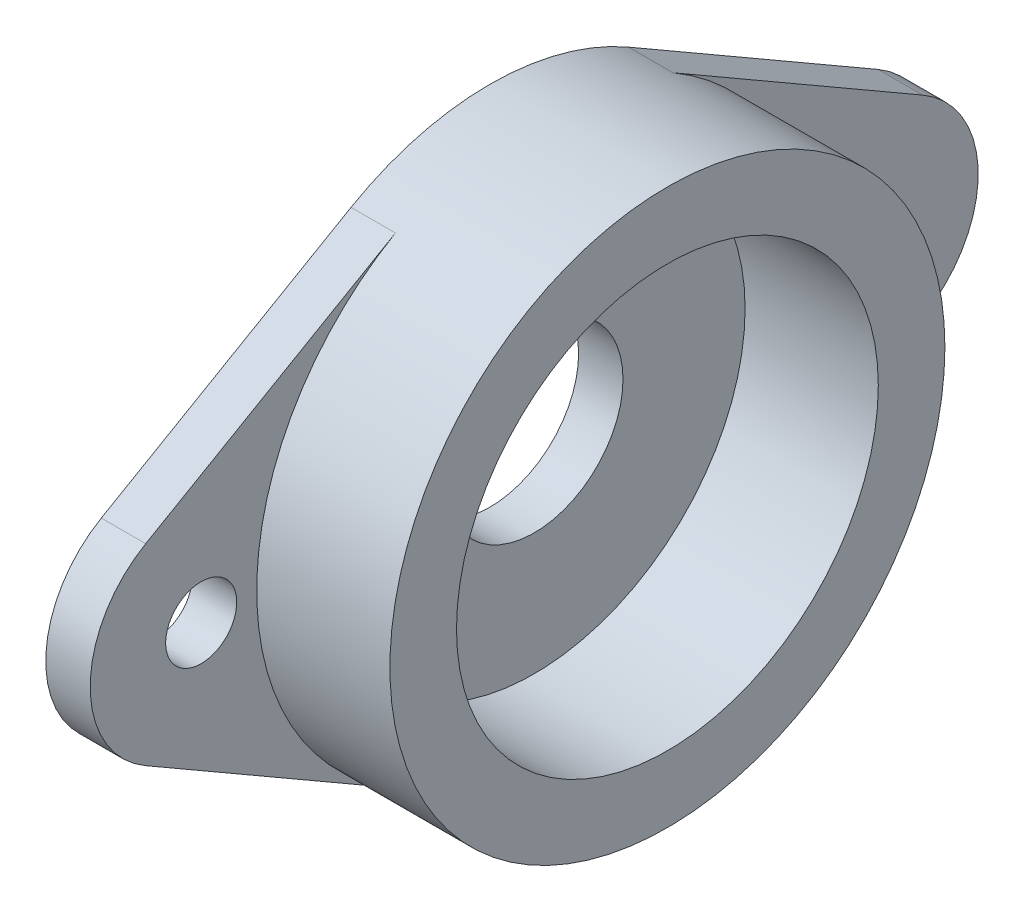
SolidWorks part; units mm, degrees
ref_plane "Front Plane" through (0, 0, 0) normal (0, 0, 1) x (1, 0, 0)
ref_plane "Top Plane" through (0, 0, 0) normal (0, 1, 0) x (1, 0, 0)
ref_plane "Right Plane" through (0, 0, 0) normal (1, 0, 0) x (0, 0, -1)
sketch "Sketch1" plane through (0, 0, 0) normal (1, 0, 0) x (0, 0, -1)
  line L0 (0, 0) -> (0, 7304.3141) construction
  line L1 (-17.5, 4.3301) -> (-6.25, 10.8253)
  line L2 (-17.5, -4.3301) -> (-6.25, -10.8253)
  line L3 (17.5, -4.3301) -> (6.25, -10.8253)
  line L4 (17.5, 4.3301) -> (6.25, 10.8253)
  circle A2 centre (0, 0) radius 9.5
  circle A3 centre (0, 0) radius 12.5
  arc A4 (-17.5, -4.3301) -> (-17.5, 4.3301) centre (-15, 0) cw
  circle A5 centre (-15, 0) radius 1.6
  circle A6 centre (15, 0) radius 1.6
  arc A7 (17.5, -4.3301) -> (17.5, 4.3301) centre (15, 0) ccw
  circle A8 centre (0, 0) radius 4
  dimension "D1" = 19
  dimension "D2" = 12.5
  dimension "D4" = 3.2
  dimension "D5" = 5
  dimension "D6" = 8
  dimension "D3" = 15
extrude "Boss-Extrude1" add sketch "Sketch1" along normal blind 2 contours A4 L2 A3 L1 A5 | L3 A7 L4 A3 A6 region at (0, 7.3556, 11.7468) region at (0, 7.3556, -11.7468)
extrude "Boss-Extrude2" add sketch "Sketch1<5>" along normal offset from surface (8 mm away) 6 contours L0 A3 A2 | A3 L0 A2 region at (0, 11.7326, -3.1437) up to face at (2, 0, 13.4) offset beyond the face yes
sketch "Sketch1<5>" plane through (0, 0, 0) normal (1, 0, 0) x (0, 0, -1) same geometry as "Sketch1"
extrude "Boss-Extrude3" add sketch "Sketch1<6>" along normal blind 2 contours L0 A2 A8 | A2 L0 A8 region at (0, 6.5275, -6.5275)
sketch "Sketch1<6>" plane through (0, 0, 0) normal (1, 0, 0) x (0, 0, -1) same geometry as "Sketch1"
